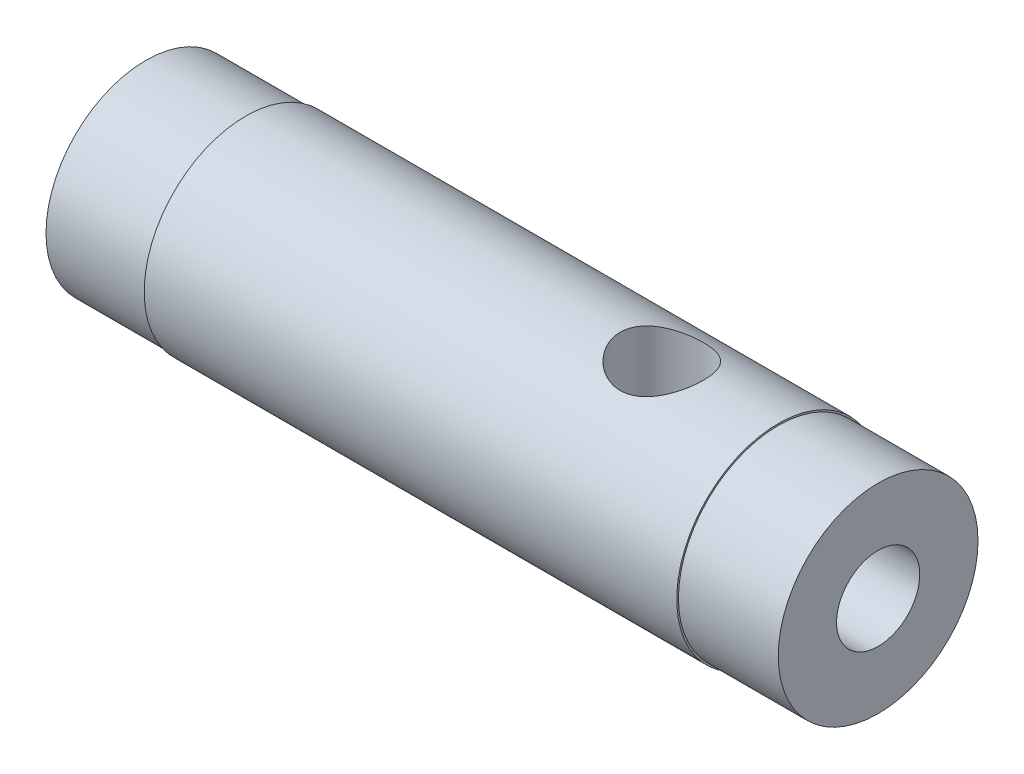
SolidWorks part; units mm, degrees
material "Rostfreier Stahl (ferritisch)"
ref_plane "Ebene vorne" through (0, 0, 0) normal (0, 0, 1) x (1, 0, 0)
ref_plane "Ebene oben" through (0, 0, 0) normal (0, 1, 0) x (1, 0, 0)
ref_plane "Ebene rechts" through (0, 0, 0) normal (1, 0, 0) x (0, 0, -1)
sketch "Skizze1" plane through (0, 0, 0) normal (0, 0, 1) x (1, 0, 0)
  line L0 (-11, 3) -> (-8, 3)
  line L1 (-8, 3) -> (-8, 3.05)
  line L2 (-8, 3.05) -> (8, 3.05)
  line L3 (8, 3.05) -> (8, 3)
  line L4 (8, 3) -> (11, 3)
  line L5 (11, 3) -> (11, 0)
  line L6 (11, 0) -> (-11, 0)
  line L7 (-11, 0) -> (-11, 3)
  line L8 (-97.1118, 0) -> (-127.7911, 0) construction
  line L9 (0, 3.05) -> (0, 0) construction
  dimension "D1" = 3
  dimension "D2" = 6
  dimension "D3" = 6.1
  dimension "D4" = 16
revolve "Rotation1" add sketch "Skizze1" angle 360 about L8
sketch "Skizze2" plane through (11, 0, 0) normal (1, 0, 0) x (0, 0, -1)
  circle A0 centre (0, 0) radius 1
  circle A1 centre (0, 0) radius 1.25
  dimension "D1" = 2
  dimension "D2" = 2.5
extrude "Schnitt-Linear austragen1" cut sketch "Skizze2" against normal blind 10 contours A0
extrude "Schnitt-Linear austragen2" cut sketch "Skizze2<3>" against normal blind 2
sketch "Skizze2<3>" plane through (11, 0, 0) normal (1, 0, 0) x (0, 0, -1) same geometry as "Skizze2"
sketch "Skizze3" plane through (0, 0, 0) normal (0, 1, 0) x (1, 0, 0)
  line L0 (0, 0) -> (4.5, 0) construction
  circle A0 centre (4.5, 0) radius 1.25
  circle A1 centre (4.5, 0) radius 1.5 construction
  dimension "D1" = 2.5
  dimension "D3" = 3
  dimension "D2" = 4.5
extrude "Schnitt-Linear austragen3" cut sketch "Skizze3" along normal through all
